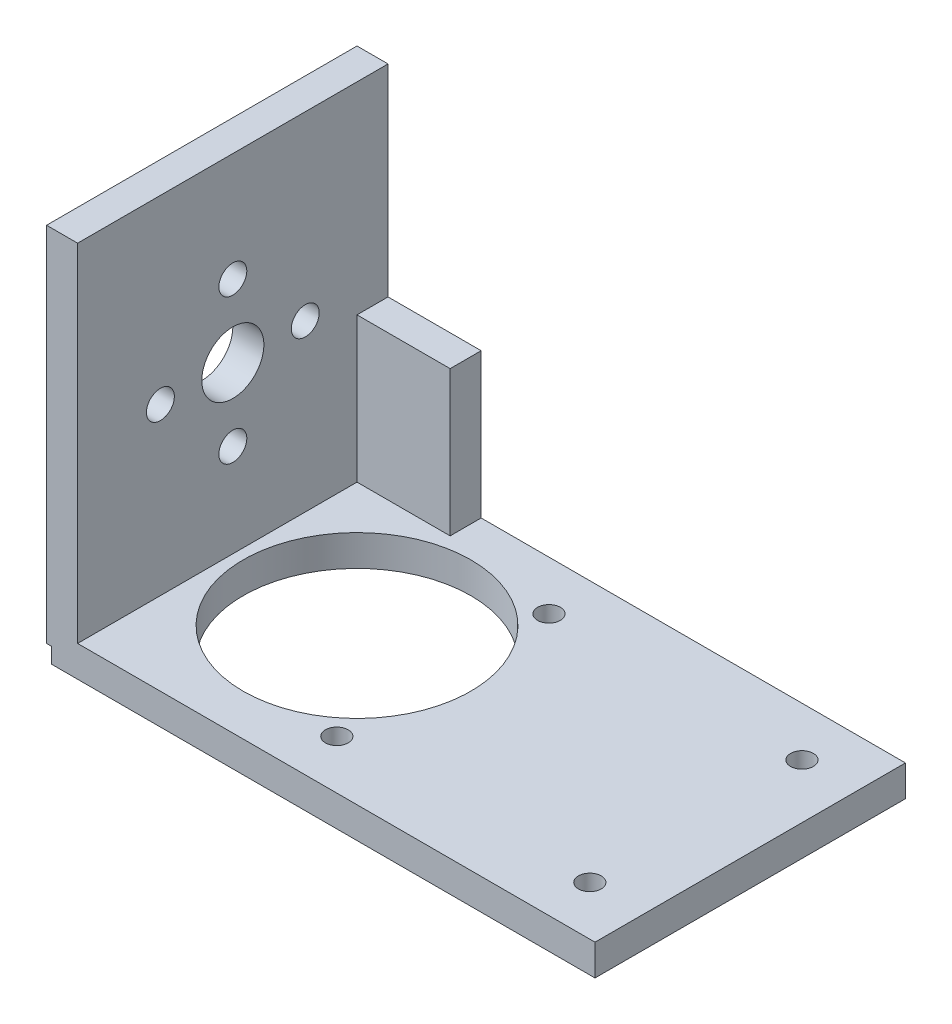
SolidWorks part; units mm, degrees
ref_plane "Front Plane" through (0, 0, 0) normal (0, 0, 1) x (1, 0, 0)
ref_plane "Top Plane" through (0, 0, 0) normal (0, 1, 0) x (1, 0, 0)
ref_plane "Right Plane" through (0, 0, 0) normal (1, 0, 0) x (0, 0, -1)
ref_plane "PZ_m15_000" through (0, 0, -15) normal (0, 0, 1) x (1, 0, 0)
sketch "S_box1" plane through (0, 0, -15) normal (0, 0, 1) x (1, 0, 0)
  line L0 (-15, -17.5) -> (-12, -17.5)
  line L1 (-12, -17.5) -> (-12, 17.5)
  line L2 (-12, 17.5) -> (-15, 17.5)
  line L3 (-15, 17.5) -> (-15, -17.5)
  dimension "P1" = 15
  dimension "P2" = 17.5
  dimension "P3" = 12
  dimension "P4" = 17.5
  dimension "P5" = 12
  dimension "P6" = 17.5
  dimension "P7" = 15
  dimension "P8" = 17.5
extrude "Boss_1" add sketch "S_box1" along normal blind 30
sketch "S_box2" plane through (0, 0, -15) normal (0, 0, 1) x (1, 0, 0)
  line L0 (-14.5, -19) -> (38, -19)
  line L1 (38, -19) -> (38, -16)
  line L2 (38, -16) -> (-14.5, -16)
  line L3 (-14.5, -16) -> (-14.5, -19)
  dimension "P1" = 14.5
  dimension "P2" = 19
  dimension "P3" = 38
  dimension "P4" = 19
  dimension "P5" = 38
  dimension "P6" = 16
  dimension "P7" = 14.5
  dimension "P8" = 16
extrude "Boss_2" add sketch "S_box2" along normal blind 30
sketch "S_box3" plane through (0, 0, -15) normal (0, 0, 1) x (1, 0, 0)
  line L0 (-14.5, -18.5) -> (-3, -18.5)
  line L1 (-3, -18.5) -> (-3, -2)
  line L2 (-3, -2) -> (-14.5, -2)
  line L3 (-14.5, -2) -> (-14.5, -18.5)
  dimension "P1" = 14.5
  dimension "P2" = 18.5
  dimension "P3" = 3
  dimension "P4" = 18.5
  dimension "P5" = 3
  dimension "P6" = 2
  dimension "P7" = 14.5
  dimension "P8" = 2
extrude "Boss_3" add sketch "S_box3" along normal blind 3
ref_plane "PX_m15_100" through (-15.1, 0, 0) normal (1, 0, 0) x (0, 0, -1)
sketch "S_hole4" plane through (-15.1, 0, 0) normal (1, 0, 0) x (0, 0, -1)
  circle A0 centre (0, 0) radius 3
  dimension "D1_S_hole4" = 6
extrude "Hole_4" cut sketch "S_hole4" along normal blind 3.2
sketch "S_hole5" plane through (-15.1, 0, 0) normal (1, 0, 0) x (0, 0, -1)
  circle A0 centre (0, 7) radius 1.35
  dimension "D1_S_hole5" = 2.7
  dimension "P2" = 7
extrude "Hole_5" cut sketch "S_hole5" along normal blind 3.2
sketch "S_hole6" plane through (-15.1, 0, 0) normal (1, 0, 0) x (0, 0, -1)
  circle A0 centre (-7, 0) radius 1.35
  dimension "D1_S_hole6" = 2.7
  dimension "P2" = 7
extrude "Hole_6" cut sketch "S_hole6" along normal blind 3.2
sketch "S_hole7" plane through (-15.1, 0, 0) normal (1, 0, 0) x (0, 0, -1)
  circle A0 centre (0, -7) radius 1.35
  dimension "D1_S_hole7" = 2.7
  dimension "P2" = 7
extrude "Hole_7" cut sketch "S_hole7" along normal blind 3.2
sketch "S_hole8" plane through (-15.1, 0, 0) normal (1, 0, 0) x (0, 0, -1)
  circle A0 centre (7, 0) radius 1.35
  dimension "D1_S_hole8" = 2.7
  dimension "P2" = 7
extrude "Hole_8" cut sketch "S_hole8" along normal blind 3.2
ref_plane "PY_m19_100" through (0, -19.1, 0) normal (0, 1, 0) x (1, 0, 0)
sketch "S_hole9" plane through (0, -19.1, 0) normal (0, 1, 0) x (1, 0, 0)
  circle A0 centre (0, 0) radius 11
  dimension "D1_S_hole9" = 22
extrude "Hole_9" cut sketch "S_hole9" along normal blind 3.2
sketch "S_hole10" plane through (0, -19.1, 0) normal (0, 1, 0) x (1, 0, 0)
  circle A0 centre (8.3, 10.25) radius 1.1
  dimension "D1_S_hole10" = 2.2
  dimension "P2" = 8.3
  dimension "P3" = 10.25
extrude "Hole_10" cut sketch "S_hole10" along normal blind 3.2
sketch "S_hole11" plane through (0, -19.1, 0) normal (0, 1, 0) x (1, 0, 0)
  circle A0 centre (8.3, -10.25) radius 1.1
  dimension "D1_S_hole11" = 2.2
  dimension "P2" = 8.3
  dimension "P3" = 10.25
extrude "Hole_11" cut sketch "S_hole11" along normal blind 3.2
sketch "S_hole12" plane through (0, -19.1, 0) normal (0, 1, 0) x (1, 0, 0)
  circle A0 centre (32.75, 10.25) radius 1.1
  dimension "D1_S_hole12" = 2.2
  dimension "P2" = 32.75
  dimension "P3" = 10.25
extrude "Hole_12" cut sketch "S_hole12" along normal blind 3.2
sketch "S_hole13" plane through (0, -19.1, 0) normal (0, 1, 0) x (1, 0, 0)
  circle A0 centre (32.75, -10.25) radius 1.1
  dimension "D1_S_hole13" = 2.2
  dimension "P2" = 32.75
  dimension "P3" = 10.25
extrude "Hole_13" cut sketch "S_hole13" along normal blind 3.2
equation "\"plate_t\" = 3"
equation "\"clearance\" = 0.4"
